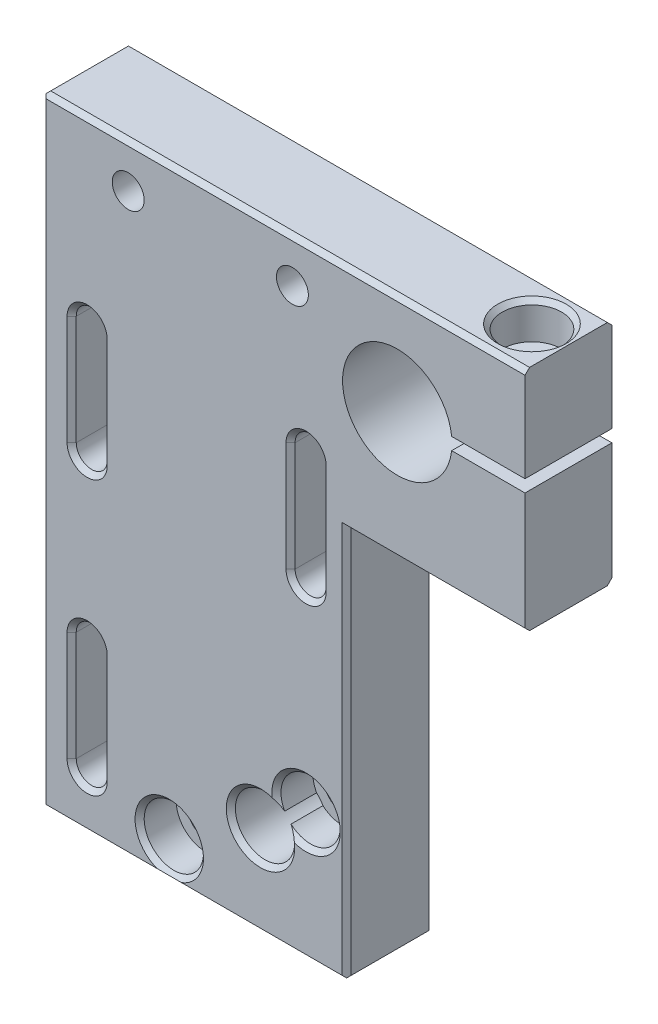
SolidWorks part; units mm, degrees
ref_plane "Front Plane" through (0, 0, 0) normal (0, 0, 1) x (1, 0, 0)
ref_plane "Top Plane" through (0, 0, 0) normal (0, 1, 0) x (1, 0, 0)
ref_plane "Right Plane" through (0, 0, 0) normal (1, 0, 0) x (0, 0, -1)
sketch "Sketch1" plane through (0, 0, 0) normal (0, 0, 1) x (1, 0, 0)
  line L0 (0, 0) -> (24.45, 0)
  line L1 (30, -16) -> (30, 43) construction
  line L3 (24.45, 43) -> (24.45, 0)
  line L4 (24.45, 0) -> (24.6859, 0.0472)
  line L6 (24.45, 43) -> (58.5, 43)
  line L8 (0, 68) -> (58.5, 68)
  line L9 (58.5, 43) -> (58.5, 68)
  line L10 (0, 0) -> (-9, 0)
  line L12 (0, 68) -> (-9, 68)
  line L13 (-9, 0) -> (-9, 68)
  circle A0 centre (5, 4) radius 2
  circle A1 centre (20, 14) radius 2
  circle A2 centre (15, 10) radius 3.25
  circle A3 centre (5, 4) radius 3.25
  circle A4 centre (30, -16) radius 6.55
  circle A5 centre (20, 14) radius 3.25
  dimension "D3" = 4
  dimension "D7" = 4
  dimension "D10" = 6.5
  dimension "D13" = 13.1
  dimension "D19" = 6.5
  dimension "D20" = 6.5
  dimension "D1" = 24.45
  dimension "D2" = 4
  dimension "D4" = 5
  dimension "D5" = 20
  dimension "D6" = 14
  dimension "D8" = 10
  dimension "D9" = 15
  dimension "D11" = 30
  dimension "D12" = 16
  dimension "D14" = 43
  dimension "D15" = 58.5
  dimension "D16" = 67.5
  dimension "D17" = 9
  dimension "D18" = 68
extrude "Boss-Extrude1" add sketch "Sketch1" along normal blind 9.525 contours L13 L10 L0 L3 L6 L9 L8 L12 A2 A1 A0 region at (17.0339, 40.8583, 0)
extrude "Boss-Extrude3" add sketch "Sketch1<4>" along normal blind 5.525 contours A2 A5 A1 | A3 A0 region at (17.6096, 12.0877, 0) region at (1.8419, 4, 0)
sketch "Sketch1<4>" plane through (0, 0, 0) normal (0, 0, 1) x (1, 0, 0) same geometry as "Sketch1"
sketch "Sketch3" plane through (0, 0, 9.525) normal (0, 0, 1) x (1, 0, 0)
  line L0 (-2.3, 18) -> (-2.3, 6)
  line L1 (-9, 0) -> (-9, 68) construction
  line L2 (24.45, 0) -> (-9, 0) construction
  line L3 (-5.7, 18) -> (-5.7, 6)
  line L4 (-5.7, 48) -> (-5.7, 36)
  line L5 (-2.3, 48) -> (-2.3, 36)
  line L6 (18.3, 48) -> (18.3, 36)
  line L7 (21.7, 48) -> (21.7, 36)
  arc A0 (-2.3, 18) -> (-5.7, 18) centre (-4, 18) ccw
  arc A1 (-2.3, 48) -> (-5.7, 48) centre (-4, 48) ccw
  arc A2 (21.7, 48) -> (18.3, 48) centre (20, 48) ccw
  arc A7 (-5.7, 6) -> (-2.3, 6) centre (-4, 6) ccw
  arc A8 (-5.7, 36) -> (-2.3, 36) centre (-4, 36) ccw
  arc A11 (18.3, 36) -> (21.7, 36) centre (20, 36) ccw
  dimension "D3" = 3.4
  dimension "D4" = 3.4
  dimension "D5" = 3.4
  dimension "D6" = 5
  dimension "D7" = 6
  dimension "D8" = 12
  dimension "D11" = 3.4
  dimension "D12" = 3.4
  dimension "D13" = 3.4
  dimension "D1" = 24
  dimension "D2" = 30
  dimension "D9" = 12
  dimension "D10" = 12
  dimension "D14" = 12
  dimension "D15" = 12
  dimension "D16" = 12
  dimension "D17" = 12
  dimension "D18" = 12
  dimension "D19" = 12
extrude "Cut-Extrude1" cut sketch "Sketch3" against normal through all
sketch "Sketch4" plane through (0, 0, 0) normal (0, 0, -1) x (-1, 0, 0)
  line L4 (-16.75, 36) -> (-16.75, 48)
  line L5 (-23.25, 48) -> (-23.25, 36)
  line L8 (0.75, 48) -> (0.75, 36)
  line L9 (7.25, 36) -> (7.25, 48)
  line L12 (7.25, 6) -> (7.25, 18)
  line L13 (0.75, 17.9953) -> (0.75, 5.9953)
  arc A0 (2.3, 6) -> (5.7, 6) centre (4, 6) ccw construction
  arc A1 (5.7, 18) -> (2.3, 18) centre (4, 18) ccw construction
  arc A2 (2.3, 36) -> (5.7, 36) centre (4, 36) ccw construction
  arc A3 (5.7, 48) -> (2.3, 48) centre (4, 48) ccw construction
  arc A4 (-23.25, 36) -> (-16.75, 36) centre (-20, 36) ccw
  arc A5 (-16.75, 48) -> (-23.25, 48) centre (-20, 48) ccw
  arc A6 (-21.7, 36) -> (-18.3, 36) centre (-20, 36) ccw construction
  arc A7 (-18.3, 48) -> (-21.7, 48) centre (-20, 48) ccw construction
  arc A8 (0.75, 36) -> (7.25, 36) centre (4, 36) ccw
  arc A9 (7.25, 48) -> (0.75, 48) centre (4, 48) ccw
  arc A12 (0.75, 5.9953) -> (7.25, 6) centre (4, 6) ccw
  arc A13 (7.25, 18) -> (0.75, 17.9953) centre (4, 18) ccw
  dimension "D4" = 3.25
  dimension "D1" = 3.25
  dimension "D6" = 3.25
  dimension "D7" = 3.25
  dimension "D11" = 3.25
  dimension "D12" = 3.25
  dimension "D2" = 12
  dimension "D3" = 12
  dimension "D5" = 6.5
  dimension "D8" = 12
  dimension "D9" = 12
  dimension "D10" = 6.5
  dimension "D13" = 12
  dimension "D14" = 12
  dimension "D15" = 6.5
extrude "Cut-Extrude2" cut sketch "Sketch4" against normal blind 5.525
chamfer "Chamfer1" distance 0.5 angle 45 1 edges at (-9, 68, 4.7625)
chamfer "Chamfer2" distance 0.5 angle 45 4 edges at (-9, 0, 4.7625) (24.45, 0, 4.7625) (58.5, 43, 4.7625) (58.5, 68, 4.7625)
chamfer "Chamfer3" distance 0.5 angle 45 12 edges at (24.75, 68, 0) (58.5, 55.5, 0) (41.225, 43, 0) (24.45, 21.75, 0) (24.75, 68, 9.525) (58.5, 55.5, 9.525) (41.225, 43, 9.525) (24.45, 21.75, 9.525) (7.725, 0, 0) (7.725, 0, 9.525) (-9, 34, 0) (-9, 34, 9.525)
chamfer "Chamfer4" distance 0.5 angle 45 15 edges at (20, 34.3, 9.525) (21.7, 42, 9.525) (20, 49.7, 9.525) (18.3, 42, 9.525) (-4, 34.3, 9.525) (-2.3, 42, 9.525) (-4, 49.7, 9.525) (-5.7, 42, 9.525) (-5.7, 12, 9.525) (-4, 4.3, 9.525) (-2.3, 12, 9.525) (-4, 19.7, 9.525) (8.25, 4, 9.525) (22.5378, 16.0303, 9.525) (12.4622, 7.9697, 9.525)
sketch "Sketch6" plane through (0, 0, 9.525) normal (0, 0, 1) x (1, 0, 0)
  line L0 (0, 68) -> (58.5, 68) construction
  line L1 (22.2, 48) -> (22.2, 36) construction
  line L2 (30, 57.675) -> (50, 57.675)
  line L3 (30, 57.675) -> (30, 56.325)
  line L4 (30, 56.325) -> (50, 56.325)
  line L5 (50, 57.675) -> (50, 56.325)
  line L6 (79, 1) -> (29, 1)
  line L7 (79, 1) -> (79, 51)
  line L8 (79, 51) -> (29, 51)
  line L9 (29, 1) -> (29, 51)
  line L10 (-9, 0) -> (-9, 68) construction
  circle A0 centre (30, 57) radius 6
  dimension "D1" = 12
  dimension "D2" = 73
  dimension "D3" = 1.35
  dimension "D4" = 0.675
  dimension "D5" = 20
  dimension "D6" = 17
  dimension "D7" = 38
  dimension "D8" = 50
  dimension "D9" = 50
sketch "Sketch7" plane through (0, 0, 9.525) normal (0, 0, 1) x (1, 0, 0)
  line L0 (0, 68) -> (58.5, 68) construction
  line L1 (58.5, 43) -> (44, 43)
  line L2 (58.5, 43) -> (58.5, 68)
  line L3 (58.5, 68) -> (44, 68)
  line L4 (44, 43) -> (44, 68)
  dimension "D1" = 14
extrude "Cut-Extrude4" cut sketch "Sketch7" against normal through all
extrude "Cut-Extrude5" cut sketch "Sketch6" against normal through all contours L2 A0 L4 L3 | L4 A0 L2 L3 | A0 L4 L5 L2 region at (29.7696, 57, 9.525) region at (32.9937, 57, 9.525) region at (42.9937, 57, 9.525)
sketch "Sketch9" plane through (0, 0, 9.525) normal (0, 0, 1) x (1, 0, 0)
  line L0 (-8.5, 68) -> (44, 68) construction
  line L1 (-9, 0.5) -> (-9, 67.5) construction
  circle A0 centre (0.5, 63.2375) radius 1.75
  circle A1 centre (18.5, 63.2375) radius 1.75
  circle A2 centre (0.5, 63.2375) radius 3.25
  circle A3 centre (18.5, 63.2375) radius 3.25
  dimension "D1" = 3.5
  dimension "D2" = 3.5
  dimension "D3" = 6.5
  dimension "D6" = 6.5
  dimension "D4" = 4.7625
  dimension "D5" = 4.7625
  dimension "D7" = 9.5
  dimension "D8" = 18
sketch "Sketch10" plane through (0, 0, 0) normal (0, 0, -1) x (-1, 0, 0)
  circle A0 centre (-18.5, 63.2375) radius 1.75 construction
  circle A1 centre (-18.5, 63.2375) radius 3.25 construction
  circle A2 centre (-0.5, 63.2375) radius 1.75 construction
  circle A3 centre (-0.5, 63.2375) radius 3.25 construction
  circle A4 centre (-18.5, 63.2375) radius 1.75
  circle A5 centre (-18.5, 63.2375) radius 3.25
  circle A6 centre (-0.5, 63.2375) radius 1.75
  circle A7 centre (-0.5, 63.2375) radius 3.25
extrude "Cut-Extrude6" cut sketch "Sketch10" against normal blind 4
extrude "Cut-Extrude7" cut sketch "Sketch9" against normal through all contours A0 | A1 region at (0.5, 63.2375, 9.525) region at (18.5, 63.2375, 9.525)
chamfer "Chamfer5" distance 0.5 angle 45 2 edges at (-2.75, 63.2375, 0) (15.25, 63.2375, 0)
sketch "Sketch12" plane through (0, 68, 0) normal (0, 1, 0) x (1, 0, 0)
  line L0 (44, -0.5) -> (44, -9.025) construction
  line L1 (-8.5, 0) -> (44, 0) construction
  circle A0 centre (40, -4.7625) radius 1.75
  circle A1 centre (40, -4.7625) radius 3.25
  dimension "D3" = 3.5
  dimension "D4" = 6.5
  dimension "D1" = 4
  dimension "D2" = 4.7625
extrude "Cut-Extrude8" cut sketch "Sketch12" against normal up to surface (10.325 mm away) contours A0 region at (40, 68, 4.7625) up to face at (39.981, 57.675, 4.7625)
sketch "Sketch13" plane through (0, 43, 0) normal (0, -1, 0) x (1, 0, 0)
  line L0 (44, 0) -> (23.95, 0) construction
  line L1 (44, 0.5) -> (44, 9.025) construction
  circle A0 centre (40, 4.7625) radius 1.2195
  dimension "D1" = 2.439
  dimension "D2" = 4.7625
  dimension "D3" = 4
extrude "Cut-Extrude9" cut sketch "Sketch13" against normal up to surface (13.325 mm away) up to face at (39.981, 56.325, 4.7625)
extrude "Cut-Extrude10" cut sketch "Sketch12<3>" against normal blind 4
sketch "Sketch12<3>" plane through (0, 68, 0) normal (0, 1, 0) x (1, 0, 0) same geometry as "Sketch12"
chamfer "Chamfer6" distance 0.5 angle 45 1 edges at (36.75, 68, 4.7625)
